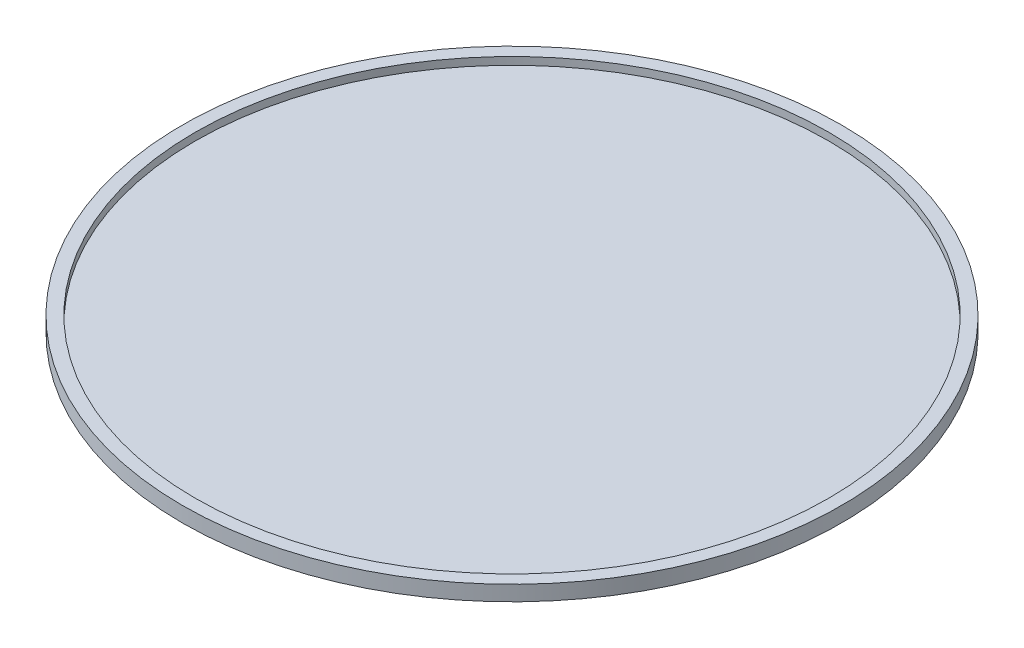
SolidWorks part; units mm, degrees
ref_plane "Front Plane" through (0, 0, 0) normal (0, 0, 1) x (1, 0, 0)
ref_plane "Top Plane" through (0, 0, 0) normal (0, 1, 0) x (1, 0, 0)
ref_plane "Right Plane" through (0, 0, 0) normal (1, 0, 0) x (0, 0, -1)
sketch "Sketch1" plane through (0, 0, 0) normal (0, 1, 0) x (1, 0, 0)
  circle A0 centre (0, 0) radius 125
extrude "Boss-Extrude1" add sketch "Sketch1" along normal blind 3
sketch "Sketch2" plane through (0, 3, 0) normal (0, 1, 0) x (1, 0, 0)
  circle A0 centre (0, 0) radius 130
  circle A1 centre (0, 0) radius 125
extrude "Boss-Extrude2" add sketch "Sketch2" along normal blind 3 and the other way up to surface (3 mm away) other way up to face at (0, 0, 125)
